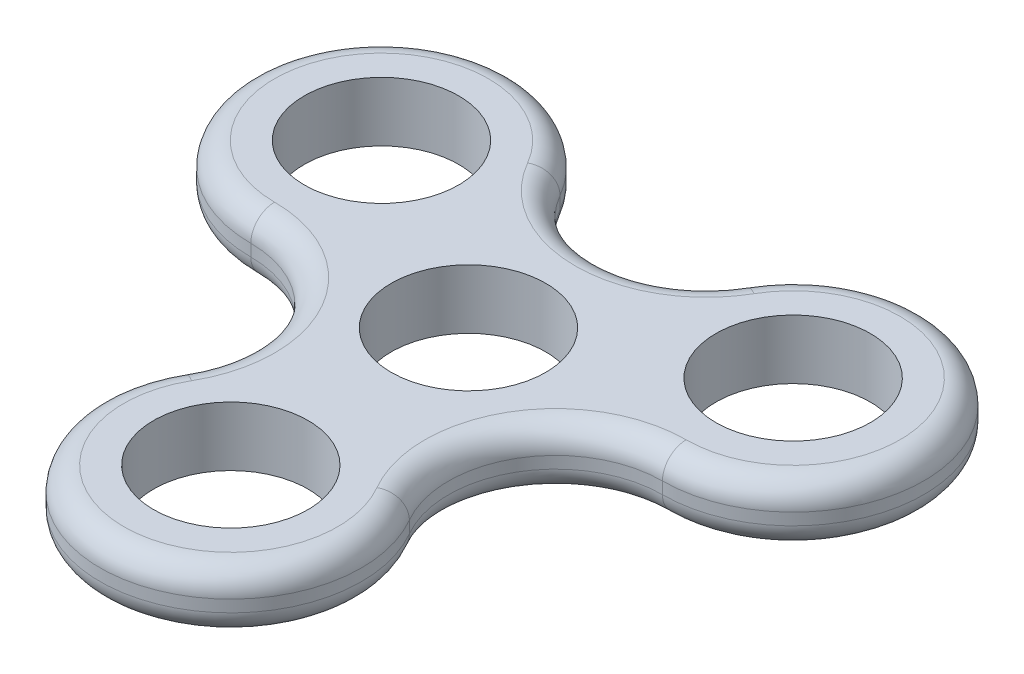
SolidWorks part; units mm, degrees
ref_plane "Alzado" through (0, 0, 0) normal (0, 0, 1) x (1, 0, 0)
ref_plane "Planta" through (0, 0, 0) normal (0, 1, 0) x (1, 0, 0)
ref_plane "Vista lateral" through (0, 0, 0) normal (1, 0, 0) x (0, 0, -1)
sketch "Croquis1" plane through (0, 0, 0) normal (0, 1, 0) x (1, 0, 0)
  line L0 (0, -20) -> (0, 20) construction
  line L1 (17.3205, -10) -> (-17.3205, 10) construction
  line L2 (17.3205, 10) -> (-17.3205, -10) construction
  circle A0 centre (0, 0) radius 7 construction
  circle A1 centre (0, -20) radius 7 construction
  circle A2 centre (-17.3205, 10) radius 7 construction
  circle A3 centre (17.3205, 10) radius 7 construction
  arc A4 (17.3205, -1) -> (7.7942, 15.5) centre (17.3205, 10) ccw
  arc A5 (-9.5263, -14.5) -> (9.5263, -14.5) centre (0, -20) ccw
  arc A6 (-7.7942, 15.5) -> (-17.3205, -1) centre (-17.3205, 10) ccw
  circle A7 centre (0, 0) radius 20 construction
  arc A8 (-9.5263, -14.5) -> (-17.3205, -1) centre (-17.3205, -10) ccw
  arc A9 (17.3205, -1) -> (9.5263, -14.5) centre (17.3205, -10) ccw
  arc A10 (-7.7942, 15.5) -> (7.7942, 15.5) centre (0, 20) ccw
  circle A11 centre (0, 0) radius 6.6 construction
  circle A12 centre (17.3205, 10) radius 11 construction
  circle A13 centre (-17.3205, 10) radius 11 construction
  circle A14 centre (0, -20) radius 11 construction
  circle A15 centre (0, -20) radius 6.6 construction
  circle A16 centre (17.3205, 10) radius 6.6 construction
  circle A17 centre (-17.3205, 10) radius 6.6 construction
  circle A18 centre (0, 0) radius 6.5
  circle A19 centre (0, -20) radius 6.5
  circle A20 centre (17.3205, 10) radius 6.5
  circle A21 centre (-17.3205, 10) radius 6.5
  point P6 (0, 0)
  point P9 (-16.8875, -9.75)
  point P10 (9.5, 19.5)
  point P11 (17.5492, -10.132)
  point P12 (-7.3875, -9.75)
  point P13 (0, 4.875)
  point P17 (26.3875, -9.75)
  point P27 (28.3205, 10)
  point P30 (11, -20)
  point P32 (-6.3205, 10)
  dimension "D1" = 60
  dimension "D3" = 4
  dimension "D2" = 60
extrude "Saliente-Extruir1" add sketch "Croquis1" along normal blind 5
fillet "Redondeo1" radius 2 12 edges at (26.8468, 5, -15.5) (9.5263, 5, 5.5) (0, 5, 31) (-9.5263, 5, 5.5) (-26.8468, 5, -15.5) (26.8468, 0, -15.5) (9.5263, 0, 5.5) (0, 0, 31) (-9.5263, 0, 5.5) (-26.8468, 0, -15.5) (0, 5, -11) (0, 0, -11)
